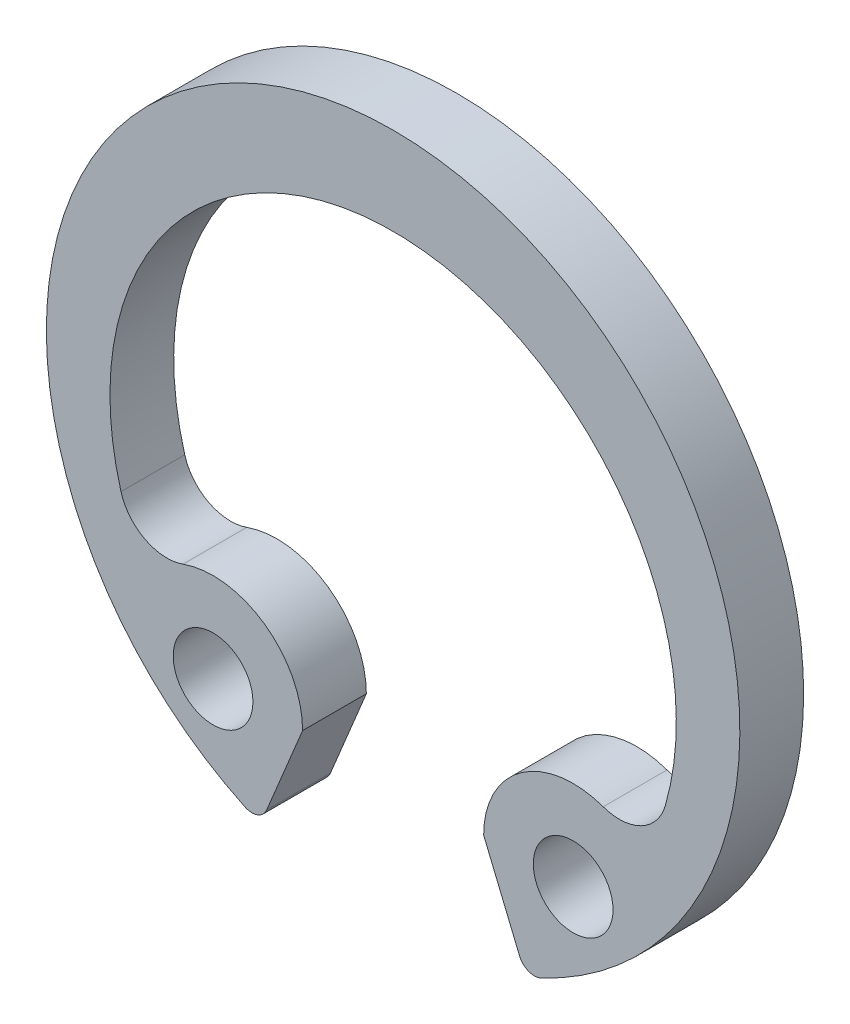
SolidWorks part; units mm, degrees
ref_plane "Front Plane" through (0, 0, 0) normal (0, 0, 1) x (1, 0, 0)
ref_plane "Top Plane" through (0, 0, 0) normal (0, 1, 0) x (1, 0, 0)
ref_plane "Right Plane" through (0, 0, 0) normal (1, 0, 0) x (0, 0, -1)
sketch "BodySke" plane through (0, 0, 0) normal (0, 0, 1) x (1, 0, 0)
  line L0 (0, -7.6074) -> (0, 7.215) construction
  line L1 (1.1357, -2.7419) -> (1.6647, -4.0189)
  line L2 (-1.1357, -2.7419) -> (-1.6647, -4.0189)
  line L3 (1.6647, -4.0189) -> (5.9992, -4.0189) construction
  line L4 (2.6886, -1.7044) -> (3.1709, -1.9042)
  line L5 (-2.6886, -1.7044) -> (-3.1709, -1.9042)
  arc A0 (1.6647, -4.0189) -> (-1.6647, -4.0189) centre (0, 0) ccw
  arc A1 (0, -3.855) -> (3.1134, -2.0133) centre (0, -0.3025) ccw construction
  circle A2 centre (2.2588, -2.7419) radius 0.5
  circle A3 centre (0, 0) radius 3.5525 construction
  circle A4 centre (-2.2588, -2.7419) radius 0.5
  arc A5 (-3.1709, -1.9042) -> (3.1709, -1.9042) centre (0, -0.3025) cw
  arc A6 (3.1134, -2.0133) -> (3.0018, -1.8998) centre (2.2588, -2.7419) ccw construction
  arc A8 (2.6886, -1.7044) -> (1.1357, -2.7419) centre (2.2588, -2.7419) ccw
  arc A9 (3.1709, -1.9042) -> (-3.1709, -1.9042) centre (0, -0.3025) ccw
  arc A10 (-2.6886, -1.7044) -> (-1.1357, -2.7419) centre (-2.2588, -2.7419) cw
  dimension "D3" = 7.105
  dimension "Hole_dia" = 1
  dimension "Groove_length" = 2.4
  dimension "D2" = 22.5
  dimension "D1" = 45
extrude "BaseBody" add sketch "BodySke" along normal blind 0.8 contours A1 L1 A0 | A1 | A1 | A9 L2 A4 region at (1.7019, -1.9085, 0)
fillet "Fillet1" radius 0.6 2 edges at (3.1709, -1.9042, 0.4) (-3.1709, -1.9042, 0.4)
fillet "Fillet2" radius 0.2 2 edges at (1.6647, -4.0189, 0.4) (-1.6647, -4.0189, 0.4)
equation "\"D3@BodySke\" = \"Groove_Diameter@BodySke\" - 1.45 * \"Groove_depth@BodySke\""
equation "\"D1@Fillet1\" = \"Hole_dia@BodySke\" * 0.6"
equation "\"D1@Fillet2\" = \"Hole_dia@BodySke\" * 0.2"
